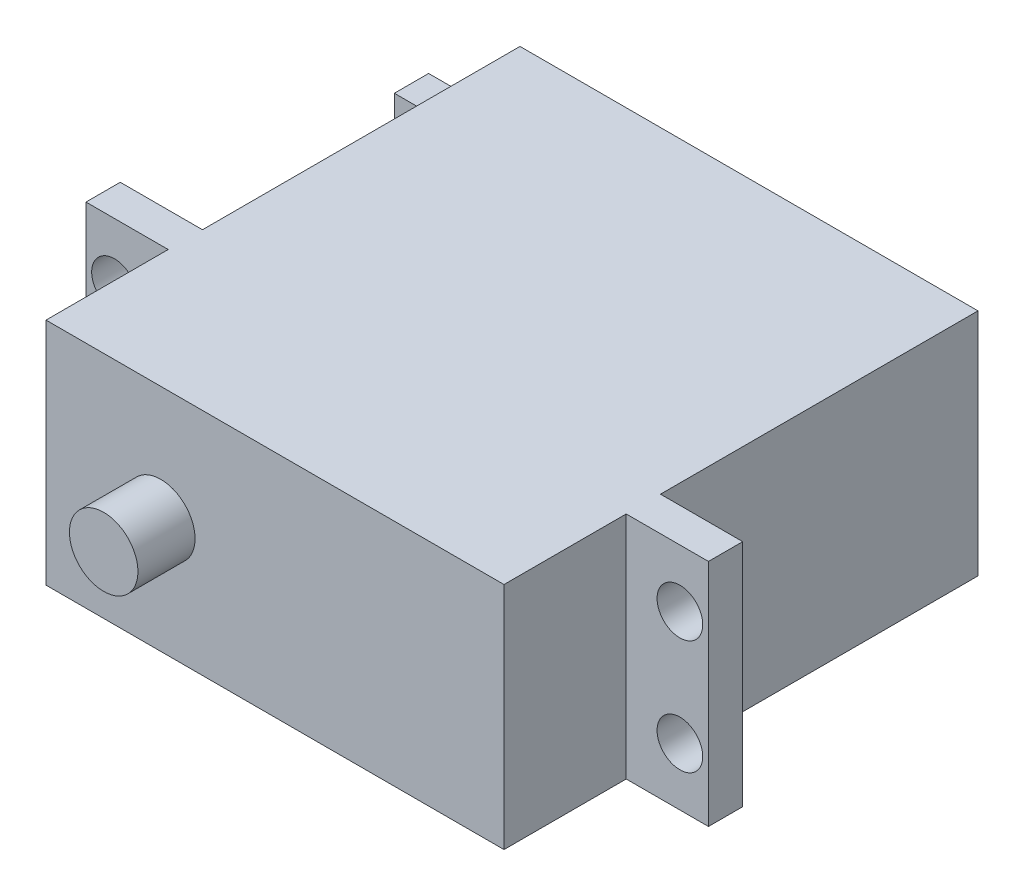
SolidWorks part; units mm, degrees
ref_plane "Top Plane" through (0, 0, 0) normal (0, 0, 1) x (1, 0, 0)
ref_plane "Right Plane" through (0, 0, 0) normal (0, 1, 0) x (1, 0, 0)
ref_plane "Front Plane" through (0, 0, 0) normal (1, 0, 0) x (0, 0, -1)
sketch "Sketch1" plane through (0, 0, 0) normal (0, 0, 1) x (1, 0, 0)
  line L0 (-10.05, 0) -> (30.05, 0) construction
  line L1 (-10.05, 10.05) -> (30.05, 10.05) construction
  line L2 (-10.05, 10.05) -> (-10.05, -10.05) construction
  line L3 (-10.05, -10.05) -> (30.05, -10.05) construction
  line L4 (30.05, 10.05) -> (30.05, -10.05) construction
  line L5 (-10.05, 10.05) -> (-17.25, 10.05) construction
  line L6 (-17.25, 10.05) -> (-17.25, -10.05) construction
  line L7 (-17.25, -10.05) -> (-10.05, -10.05) construction
  line L8 (10, 10.05) -> (10, -10.05) construction
  line L9 (37.25, -10.05) -> (30.05, -10.05) construction
  line L10 (37.25, 10.05) -> (37.25, -10.05) construction
  line L11 (30.05, 10.05) -> (37.25, 10.05) construction
  line L12 (0, -10.05) -> (0, 10.05) construction
  circle A0 centre (0, 0) radius 10 construction
  circle A1 centre (-14.75, 5) radius 2 construction
  circle A2 centre (-14.75, -5) radius 2 construction
  circle A3 centre (34.75, -5) radius 2 construction
  circle A4 centre (34.75, 5) radius 2 construction
  circle A5 centre (0, 0) radius 3
  dimension "D1" = 54.5
  dimension "D2" = 49.5
  dimension "D6" = 4
  dimension "D8" = 20
  dimension "D9" = 6
  dimension "D3" = 20.1
  dimension "D4" = 40.1
  dimension "D5" = 10
  dimension "D7" = 17.25
extrude "Boss-Extrude1" add sketch "Sketch1" against normal mid plane 5
sketch "Sketch2" plane through (0, 0, -2.5) normal (0, 0, -1) x (-1, 0, 0)
  line L1 (-30.05, 10.05) -> (10.05, 10.05)
  line L2 (-30.05, 10.05) -> (-30.05, -10.05)
  line L3 (-30.05, -10.05) -> (10.05, -10.05)
  line L4 (10.05, 10.05) -> (10.05, -10.05)
extrude "Boss-Extrude2" add sketch "Sketch2" along normal blind 41.5
sketch "Sketch3" plane through (0, 0, -44) normal (0, 0, -1) x (-1, 0, 0)
  line L1 (-37.25, 10.05) -> (-30.05, 10.05)
  line L2 (-37.25, 10.05) -> (-37.25, -10.05)
  line L3 (-37.25, -10.05) -> (-30.05, -10.05)
  line L4 (-30.05, 10.05) -> (-30.05, -10.05)
  line L5 (10.05, 10.05) -> (17.25, 10.05)
  line L6 (10.05, 10.05) -> (10.05, -10.05)
  line L7 (10.05, -10.05) -> (17.25, -10.05)
  line L8 (17.25, 10.05) -> (17.25, -10.05)
extrude "Boss-Extrude3" add sketch "Sketch3" against normal blind 3 from offset 27.8 offset against normal yes
sketch "Sketch4" plane through (0, 0, -13.2) normal (0, 0, 1) x (1, 0, 0)
  circle A0 centre (-14.75, -5) radius 2 construction
  circle A1 centre (-14.75, 5) radius 2 construction
  circle A2 centre (34.75, 5) radius 2 construction
  circle A3 centre (34.75, -5) radius 2 construction
  circle A4 centre (-14.75, -5) radius 2
  circle A5 centre (-14.75, 5) radius 2
  circle A6 centre (34.75, 5) radius 2
  circle A7 centre (34.75, -5) radius 2
extrude "Cut-Extrude1" cut sketch "Sketch4" against normal through all
sketch "Sketch5" plane through (-10.05, 0, 0) normal (-1, 0, 0) x (0, 0, 1)
  line L0 (-44, -10.05) -> (-44, 10.05) construction
  line L1 (-44, 4) -> (-41, 4)
  line L2 (-44, 4) -> (-44, -4)
  line L3 (-44, -4) -> (-41, -4)
  line L4 (-41, 4) -> (-41, -4)
  line L5 (-44, 0) -> (0, 0) construction
  line L6 (0, 10.05) -> (0, -10.05) construction
  dimension "D1" = 8
  dimension "D2" = 3
extrude "Boss-Extrude4" add sketch "Sketch5" along normal blind 8
sketch "Sketch6" plane through (0, 0, 0) normal (1, 0, 0) x (0, 0, -1)
  line L0 (-32.4992, 0) -> (61.7, 0) construction
